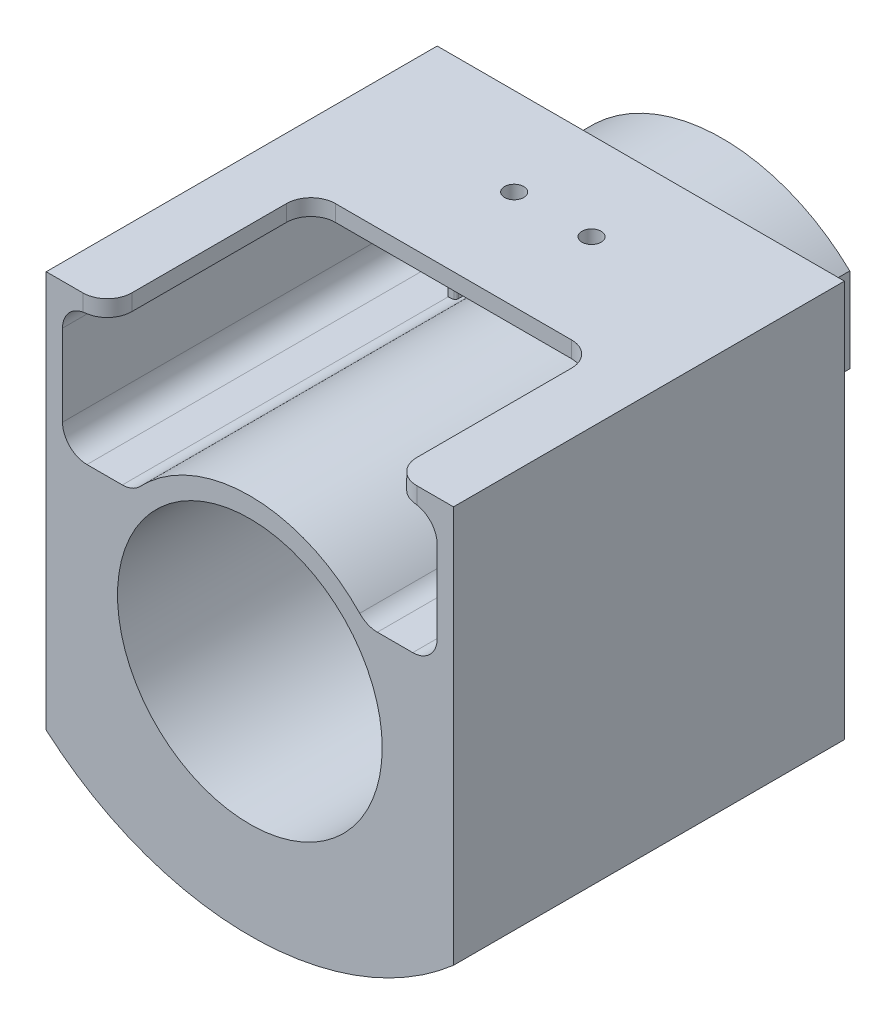
SolidWorks part; units mm, degrees
ref_plane "Front Plane" through (0, 0, 0) normal (0, 0, 1) x (1, 0, 0)
ref_plane "Top Plane" through (0, 0, 0) normal (0, 1, 0) x (1, 0, 0)
ref_plane "Right Plane" through (0, 0, 0) normal (1, 0, 0) x (0, 0, -1)
sketch "Sketch1" plane through (0, 0, 0) normal (0, 0, 1) x (1, 0, 0)
  line L1 (0, 0) -> (0, -38.1) construction
  line L2 (-25, 0) -> (-25, -28.7508)
  line L3 (25, 0) -> (25, -28.7508)
  line L4 (-25, 0) -> (-25, 20)
  line L5 (-25, 20) -> (25, 20)
  line L6 (25, 20) -> (25, 0)
  arc A0 (-25, -28.7508) -> (25, -28.7508) centre (0, 0) ccw
  dimension "D1" = 76.2
  dimension "D2" = 50
  dimension "D3" = 20
extrude "Boss-Extrude2" add sketch "Sketch1" along normal blind 48 from offset 2
sketch "Sketch2" plane through (0, 0, 50) normal (0, 0, 1) x (1, 0, 0)
  line L6 (0, 6.25) -> (0, -26.25) construction
  circle A0 centre (0, -10) radius 16.25
  dimension "D2" = 32.5
  dimension "D1" = 10
extrude "Cut-Extrude1" cut sketch "Sketch2" against normal through all both
sketch "Sketch4" plane through (0, 0, 50) normal (0, 0, 1) x (1, 0, 0)
  line L0 (-23, 18) -> (23, 18)
  line L3 (0, 20) -> (0, 6.25) construction
  line L4 (25, 20) -> (-25, 20) construction
  line L5 (23, 2) -> (14.3178, 2)
  line L6 (-23, 18) -> (-23, 2)
  line L7 (-23, 2) -> (-14.3178, 2)
  line L8 (-25, 20) -> (-25, -28.7508) construction
  line L9 (23, 18) -> (23, 2)
  circle A2 centre (0, -10) radius 16.25 construction
  arc A3 (14.3178, 2) -> (-14.3178, 2) centre (0, -10) ccw
  point P2 (0, 13.125)
  point P14 (0, 18)
  dimension "D1" = 37.3631
  dimension "D2" = 2
  dimension "D3" = 2
  dimension "D4" = 16
extrude "Cut-Extrude3" cut sketch "Sketch4" against normal through all
fillet "Fillet1" radius 3 6 edges at (23, 18, 26) (23, 2, 26) (14.3178, 2, 26) (-14.3178, 2, 26) (-23, 2, 26) (-23, 18, 26)
sketch "Sketch5" plane through (0, 20, 0) normal (0, 1, 0) x (1, 0, 0)
  line L0 (25, -50) -> (-25, -50) construction
  line L1 (-17.5, -50) -> (17.5, -50)
  line L2 (-17.5, -50) -> (-17.5, -25)
  line L3 (-17.5, -25) -> (17.5, -25)
  line L4 (17.5, -50) -> (17.5, -25)
  line L5 (0, 0) -> (0, -50) construction
  dimension "D1" = 35
  dimension "D2" = 25
extrude "Cut-Extrude4" cut sketch "Sketch5" against normal blind 10
fillet "Fillet2" radius 3 4 edges at (17.5, 19, 50) (17.5, 19, 25) (-17.5, 19, 25) (-17.5, 19, 50)
ref_plane "Plane1" through (0, 0, 14) normal (0, 0, 1) x (1, 0, 0)
sketch "Sketch6" plane through (0, 0, 14) normal (0, 0, 1) x (1, 0, 0)
  line L0 (0, -10) -> (0, 3) construction
  line L1 (0, -10) -> (-4.4463, 2.216) construction
  circle A1 centre (0, -10) radius 16.25 construction
  circle A3 centre (0, -10) radius 9.5
  circle A8 centre (0, -10) radius 16.25
  circle A9 centre (0, -10) radius 13 construction
  circle A10 centre (-4.4463, 2.216) radius 1.65
  circle A11 centre (12.216, -5.5537) radius 1.65
  circle A12 centre (4.4463, -22.216) radius 1.65
  circle A13 centre (-12.216, -14.4463) radius 1.65
  dimension "D1" = 19
  dimension "D6" = 13
  dimension "D2" = 3.5
  dimension "D3" = 3.3
  dimension "D4" = 20
  dimension "D5" = 4
extrude "Boss-Extrude3" add sketch "Sketch6" against normal blind 5
sketch "Sketch7" plane through (0, 0, 0) normal (1, 0, 0) x (0, 0, -1)
  circle A0 centre (-44, -32) radius 2.25
  circle A1 centre (-14, -32) radius 2.25
  dimension "D3" = 4.5
  dimension "D1" = 32
  dimension "D2" = 14
  dimension "D4" = 30
extrude "Cut-Extrude5" cut sketch "Sketch7" against normal through all both and the other way through all
sketch "Sketch8" plane through (0, 20, 0) normal (0, 1, 0) x (1, 0, 0)
  line L0 (0, -2) -> (0, -25) construction
  line L1 (25, -2) -> (-25, -2) construction
  line L2 (14.5, -25) -> (-14.5, -25) construction
  circle A0 centre (-4.75, -12.8) radius 1.175
  circle A1 centre (4.75, -12.8) radius 1.175
  dimension "D1" = 2.35
  dimension "D2" = 9.5
  dimension "D3" = 10.8
extrude "Cut-Extrude6" cut sketch "Sketch8" against normal up to next contours A0 | A1
sketch "Sketch9" plane through (0, 0, 50) normal (0, 0, 1) x (1, 0, 0)
  line L0 (0, -28.5) -> (0, -5) construction
  line L1 (0, -10) -> (0, -28.5) construction
  line L2 (-15.6553, 2) -> (-15.6553, 11.4123)
  line L3 (15.6553, 2) -> (15.6553, 11.4123)
  line L4 (0, 8.6815) -> (0, 17.6815) construction
  line L5 (-14.6553, 2.1716) -> (-14.6553, 10.5325)
  line L6 (14.6553, 2.1716) -> (14.6553, 10.5325)
  line L7 (-15.6553, 2) -> (-15.6553, 1)
  line L8 (15.6553, 2) -> (15.6553, 1)
  line L9 (14.6553, 2) -> (14.6553, 10.9784) construction
  line L10 (-14.6553, 2) -> (-14.6553, 10.9784) construction
  arc A0 (13.4892, 2.9245) -> (-13.4892, 2.9245) centre (0, -10) ccw construction
  arc A1 (13.4892, 2.9245) -> (-13.4892, 2.9245) centre (0, -10) ccw
  arc A3 (-15.6553, 11.4123) -> (15.6553, 11.4123) centre (0, -5) cw
  arc A4 (13.4892, 2.9245) -> (15.6553, 2) centre (15.6553, 5) ccw construction
  arc A5 (-15.6553, 2) -> (-13.4892, 2.9245) centre (-15.6553, 5) ccw construction
  arc A6 (13.4892, 2.9245) -> (15.6553, 2) centre (15.6553, 5) ccw
  arc A7 (-15.6553, 2) -> (-13.4892, 2.9245) centre (-15.6553, 5) ccw
  arc A8 (12.7671, 2.2327) -> (15.6553, 1) centre (15.6553, 5) ccw
  arc A9 (12.7671, 2.2327) -> (-12.7671, 2.2327) centre (0, -10) ccw
  arc A10 (-15.6553, 1) -> (-12.7671, 2.2327) centre (-15.6553, 5) ccw
  arc A11 (-14.3156, 11.2835) -> (14.3156, 11.2835) centre (0, -5) cw
  arc A12 (-14.6553, 10.9784) -> (14.6553, 10.9784) centre (0, -5) cw construction
  arc A13 (14.6553, 10.5325) -> (14.3156, 11.2835) centre (13.6553, 10.5325) ccw
  arc A14 (-14.6553, 10.5325) -> (-14.3156, 11.2835) centre (-13.6553, 10.5325) cw
  dimension "D1" = 9
  dimension "D2" = 1
  dimension "D4" = 1
  dimension "Ring Gear Outer Dia to Center" = 23.5
  dimension "Pinion to Ring Gear Outer Diameter" = 18.5
  dimension "D3" = 1
extrude "Boss-Extrude4" add sketch "Sketch9" along normal blind 8 and the other way blind 10 from surface contours L5 A11 L6 L2 L3 A3 A6 | L7 A10 A9 A8 L8 L2 L3 A6 region at (-15.0935, 1.7255, 50) region at (-15.3051, 6.7061, 50) starting at face at (0, 7.9303, 2)
fillet "Fillet5" radius 0.25 8 edges at (14.0281, 2.4797, -8) (-14.0281, 2.4797, -8) (14.6553, 6.352, -8) (14.5664, 10.9446, -8) (-14.6553, 6.352, -8) (-14.5664, 10.9446, -8) (0, 8.6815, -8) (0, 16.6815, -8)
fillet "Fillet6" radius 0.25 5 edges at (14.6553, 6.352, 10) (14.5664, 10.9446, 10) (-14.6553, 6.352, 10) (-14.5664, 10.9446, 10) (0, 16.6815, 10)
